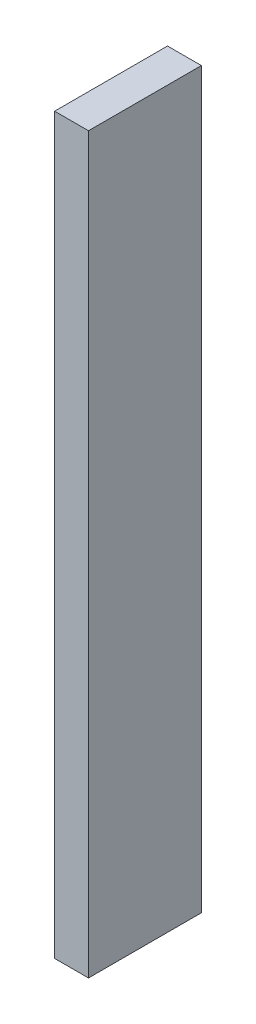
SolidWorks part; units mm, degrees
material "C-Glass Fiber"
ref_plane "xy_plane" through (0, 0, 0) normal (0, 0, 1) x (1, 0, 0)
ref_plane "zx_plane" through (0, 0, 0) normal (0, 1, 0) x (1, 0, 0)
ref_plane "yz_plane" through (0, 0, 0) normal (1, 0, 0) x (0, 0, -1)
ref_axis "x_axis" through (-80.9, 0, 0) along (1, 0, 0)
ref_axis "y_axis" through (0, -50, 0) along (0, 1, 0)
ref_axis "z_axis" through (0, 0, -80.9) along (0, 0, 1)
ref_plane "xMid_plane" through (0, 0, 0) normal (1, 0, 0) x (0, 0, -1)
ref_plane "xMin_plane" through (-1.5, 0, 0) normal (1, 0, 0) x (0, 0, -1)
ref_plane "xMax_plane" through (1.5, 0, 0) normal (1, 0, 0) x (0, 0, -1)
ref_plane "yMid_plane" through (0, 0, 0) normal (0, 1, 0) x (1, 0, 0)
ref_plane "yMin_plane" through (0, -32.5, 0) normal (0, 1, 0) x (1, 0, 0)
ref_plane "yMax_plane" through (0, 32.5, 0) normal (0, 1, 0) x (1, 0, 0)
ref_plane "zMid_plane" through (0, 0, 0) normal (0, 0, 1) x (1, 0, 0)
ref_plane "zMin_plane" through (0, 0, -5) normal (0, 0, 1) x (1, 0, 0)
ref_plane "zMax_plane" through (0, 0, 5) normal (0, 0, 1) x (1, 0, 0)
sketch "projectionXy_sketch" plane through (0, 0, 0) normal (0, 0, 1) x (1, 0, 0)
  line L0 (55, 32.5) -> (-55, 32.5) construction
  line L1 (-1.5, 32.5) -> (1.5, 32.5)
  line L2 (-1.5, 32.5) -> (-1.5, -32.5)
  line L3 (-1.5, -32.5) -> (1.5, -32.5)
  line L4 (1.5, 32.5) -> (1.5, -32.5)
  line L5 (55, -32.5) -> (-55, -32.5) construction
  line L6 (1.5, -55) -> (1.5, 55) construction
  line L7 (-1.5, -55) -> (-1.5, 55) construction
extrude "mainBody_extrude" add sketch "projectionXy_sketch" along normal up to surface (5 mm away) from surface up to plane "zMax_plane" starting at plane "zMin_plane"
sketch3d "pivotTargetRootPoint_sketch"
  point P0 (0, -20.3754, 0)
ref_point "pivotTargetRootPoint"
ref_axis "pivotTarget_axis" through (0, -20.3754, 0) along (1, 0, 0)
equation "\"D1@xMin_plane\"= \"externalParameters.this.extentX\" / 2"
equation "\"D1@xMax_plane\" = \"externalParameters.this.extentX\" / 2"
equation "\"D1@yMin_plane\" = \"externalParameters.this.extentY\" / 2"
equation "\"D1@yMax_plane\" = \"externalParameters.this.extentY\" / 2"
equation "\"D1@zMin_plane\" = \"externalParameters.this.extentZ\" / 2"
equation "\"D1@zMax_plane\" = \"externalParameters.this.extentZ\" / 2"
